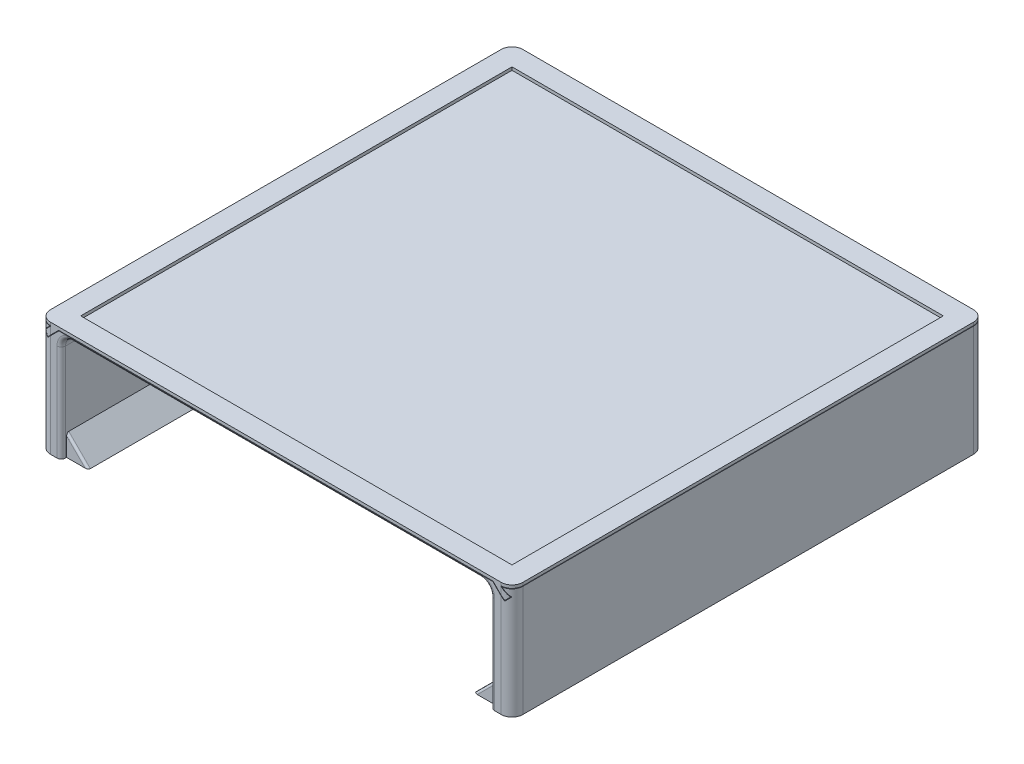
SolidWorks part; units mm, degrees
ref_plane "Front Plane" through (0, 0, 0) normal (0, 0, 1) x (1, 0, 0)
ref_plane "Top Plane" through (0, 0, 0) normal (0, 1, 0) x (1, 0, 0)
ref_plane "Right Plane" through (0, 0, 0) normal (1, 0, 0) x (0, 0, -1)
sketch "Sketch1" plane through (0, 0, 0) normal (0, 0, 1) x (1, 0, 0)
  line L0 (-99.5, -1.5) -> (99.5, -1.5)
  line L1 (-109.5, -51.5) -> (-99.5, -51.5)
  line L2 (-109.5, -51.5) -> (-109.5, 0)
  line L4 (-99.5, -51.5) -> (-99.5, -1.5)
  line L5 (0, -1.5) -> (0, 0) construction
  line L10 (-109.5, 0.2) -> (-104.2343, 0.2)
  line L14 (-100.6988, 0.2) -> (100.6988, 0.2)
  line L15 (0, 0.2) -> (0, 1.6) construction
  line L16 (109.5, 1.6) -> (-109.5, 1.6)
  line L17 (-109.5, 1.6) -> (-109.5, 0.2)
  line L21 (-109.5, 0) -> (-104.7172, 0)
  line L22 (-100.6159, 0) -> (100.6159, 0)
  line L23 (109.5, 1.2) -> (-109.5, 1.2) construction
  line L24 (109.5, 0) -> (104.7172, 0)
  line L28 (109.5, 1.6) -> (109.5, 0.2)
  line L29 (109.5, 0.2) -> (104.2343, 0.2)
  line L33 (99.5, -51.5) -> (99.5, -1.5)
  line L34 (109.5, -51.5) -> (109.5, 0)
  line L35 (109.5, -51.5) -> (99.5, -51.5)
  line L36 (-100.5, 0.2) -> (-100.5, 1.2) construction
  line L37 (-100.6988, 0.2) -> (-105.9494, -5.0506)
  line L38 (-105.9494, -5.0506) -> (-107.7172, -3.2828)
  line L39 (-107.7172, -3.2828) -> (-104.2343, 0.2)
  line L40 (-104.7172, 0) -> (-108, -3.2828)
  line L41 (-108, -3.2828) -> (-105.9494, -5.3335)
  line L42 (-105.9494, -5.3335) -> (-100.6159, 0)
  line L43 (-106.9747, -4.3081) -> (-106.8333, -4.1667) construction
  line L44 (100.6988, 0.2) -> (105.9494, -5.0506)
  line L45 (105.9494, -5.3335) -> (100.6159, 0)
  line L46 (108, -3.2828) -> (105.9494, -5.3335)
  line L47 (105.9494, -5.0506) -> (107.7172, -3.2828)
  line L48 (107.7172, -3.2828) -> (104.2343, 0.2)
  line L49 (104.7172, 0) -> (108, -3.2828)
  point P21 (0, 1.2)
  point P27 (-106.1988, -2.637)
  point P32 (-106.5288, -3.0864)
  dimension "D1" = 109.5
  dimension "D5" = 0.2
  dimension "D9" = 0.4
  dimension "MetalSheetGap" = 1
  dimension "D11" = 10
  dimension "MainBoardSize" = 50
  dimension "D13" = 9
  dimension "D3" = 45
  dimension "D4" = 1.5
  dimension "D2" = 2.5
  dimension "D7" = 0.2
  dimension "D8" = 0.2
  dimension "D10" = 3
  dimension "D6" = 1.5
extrude "Boss-Extrude1" add sketch "Sketch1" along normal mid plane 219 contours L4 L0 L33 L35 L34 L24 L49 L46 L45 L22 L42 L41 L40 L21 L2 L1
extrude "Boss-Extrude2" add sketch "Sketch1<4>" along normal mid plane 219 separate body contours L16 L17 L10 L39 L38 L37 L14 L44 L47 L48 L29 L28
sketch "Sketch1<4>" plane through (0, 0, 0) normal (0, 0, 1) x (1, 0, 0) same geometry as "Sketch1"
sketch "Sketch2" plane through (0, 0.2, 0) normal (0, -1, 0) x (1, 0, 0)
  line L1 (-100, -100) -> (100, -100)
  line L2 (-100, -100) -> (-100, 100)
  line L3 (-100, 100) -> (100, 100)
  line L4 (100, -100) -> (100, 100)
  line L5 (-100, -100) -> (100, 100) construction
  line L6 (-100, 100) -> (100, -100) construction
  point P0 (0, 0)
  dimension "D1" = 200
  dimension "D2" = 200
extrude "Cut-Extrude1" cut sketch "Sketch2" against normal through all contours L3 L4 L1 L2
fillet "Fillet1" radius 5 2 edges at (99.5, -1.5, 0) (-99.5, -1.5, 0)
sketch "Sketch3" plane through (0, 0, 0) normal (0, 0, 1) x (1, 0, 0)
  line L1 (-99.5, -1.5) -> (99.5, -1.5)
  line L2 (-99.5, -1.5) -> (-99.5, -51.5)
  line L3 (-99.5, -51.5) -> (99.5, -51.5)
  line L4 (99.5, -1.5) -> (99.5, -51.5)
extrude "Boss-Extrude3" add sketch "Sketch3" along normal mid plane 10
fillet "Fillet2" radius 5 4 edges at (-109.5, -25.75, 109.5) (-109.5, -25.75, -109.5) (109.5, -25.75, -109.5) (109.5, -25.75, 109.5)
sketch "Sketch9" plane through (0, -51.5, 0) normal (0, -1, 0) x (1, 0, 0)
  line L0 (104.5, -109.5) -> (-104.5, -109.5)
  line L1 (-109.5, -104.5) -> (-109.5, 104.5)
  line L2 (-104.5, 109.5) -> (104.5, 109.5)
  line L3 (109.5, 104.5) -> (109.5, -104.5)
  line L5 (-189.5, 189.5) -> (189.5, 189.5)
  line L6 (-189.5, 189.5) -> (-189.5, -189.5)
  line L7 (-189.5, -189.5) -> (189.5, -189.5)
  line L8 (189.5, 189.5) -> (189.5, -189.5)
  line L9 (-189.5, 189.5) -> (189.5, -189.5) construction
  line L10 (-189.5, -189.5) -> (189.5, 189.5) construction
  arc A0 (-104.5, 109.5) -> (-109.5, 104.5) centre (-104.5, 104.5) ccw
  arc A1 (-104.5, 109.5) -> (-109.5, 104.5) centre (-104.5, 104.5) ccw
  arc A2 (109.5, 104.5) -> (104.5, 109.5) centre (104.5, 104.5) ccw
  arc A3 (109.5, 104.5) -> (104.5, 109.5) centre (104.5, 104.5) ccw
  arc A4 (104.5, -109.5) -> (109.5, -104.5) centre (104.5, -104.5) ccw
  arc A5 (104.5, -109.5) -> (109.5, -104.5) centre (104.5, -104.5) ccw
  arc A6 (-109.5, -104.5) -> (-104.5, -109.5) centre (-104.5, -104.5) ccw
  arc A7 (-109.5, -104.5) -> (-104.5, -109.5) centre (-104.5, -104.5) ccw
  point P7 (0, 0)
  line M9 (-99.5, 109.5) -> (-104.5, 109.5)
  arc M10 (-104.5, 109.5) -> (-109.5, 104.5) centre (-104.5, 104.5) ccw
  line M11 (-109.5, 104.5) -> (-109.5, -104.5)
  arc M12 (-109.5, -104.5) -> (-104.5, -109.5) centre (-104.5, -104.5) ccw
  line M13 (-104.5, -109.5) -> (-99.5, -109.5)
  line M17 (99.5, -109.5) -> (104.5, -109.5)
  arc M18 (104.5, -109.5) -> (109.5, -104.5) centre (104.5, -104.5) ccw
  line M19 (109.5, -104.5) -> (109.5, 104.5)
  arc M20 (109.5, 104.5) -> (104.5, 109.5) centre (104.5, 104.5) ccw
  line M21 (104.5, 109.5) -> (99.5, 109.5)
  dimension "D1" = 80
extrude "Cut-Extrude3" cut sketch "Sketch9" against normal through all contours L8 L5 L6 L7 L2 L0 M9 M21 M20 M19 M18 M17 M13 M12 M11 M10 region at (0, -51.5, 184.1401)
fillet "Fillet4" radius 2 10 edges at (-99.5, -29, 109.5) (-98.0355, -2.9645, 109.5) (99.5, -29, 109.5) (98.0355, -2.9645, 109.5) (-99.5, -29, -109.5) (-98.0355, -2.9645, -109.5) (99.5, -29, -109.5) (98.0355, -2.9645, -109.5) (0, -1.5, 109.5) (0, -1.5, -109.5)
fillet "Fillet5" radius 1 10 edges at (-99.5, -29, -5) (-98.0355, -2.9645, -5) (0, -1.5, -5) (98.0355, -2.9645, -5) (-99.5, -29, 5) (-98.0355, -2.9645, 5) (0, -1.5, 5) (98.0355, -2.9645, 5) (99.5, -29, -5) (99.5, -29, 5)
sketch "Sketch6" plane through (0, 0, 0) normal (0, 0, 1) x (1, 0, 0)
  line L0 (-99.5, -51.5) -> (-89.5, -51.5)
  line L1 (-98.5, -51.5) -> (98.5, -51.5) construction
  line L2 (-89.5, -51.5) -> (-99.5, -41.5)
  line L3 (-99.5, -41.5) -> (-99.5, -51.5)
  dimension "D1" = 45
  dimension "D2" = 10
extrude "Boss-Extrude6" add sketch "Sketch6" against normal mid plane 214
fillet "Fillet6" radius 1 2 edges at (-94.5, -46.5, 107) (-94.5, -46.5, -107)
mirror "Mirror1" about plane through (0, 0, 0) normal (1, 0, 0) of "Fillet6", "Boss-Extrude6"
equation "\"CheckerPatternThickness\"= 0.2mm * 2'How thick the squares the pecies sit on should be"
equation "\"D9@Sketch1\"=\"CheckerPatternThickness\""
equation "\"D2@Sketch2\"=\"D1@Sketch2\""
equation "\"D7@Sketch1\"=\"D5@Sketch1\""
equation "\"D8@Sketch1\"=\"D5@Sketch1\""
